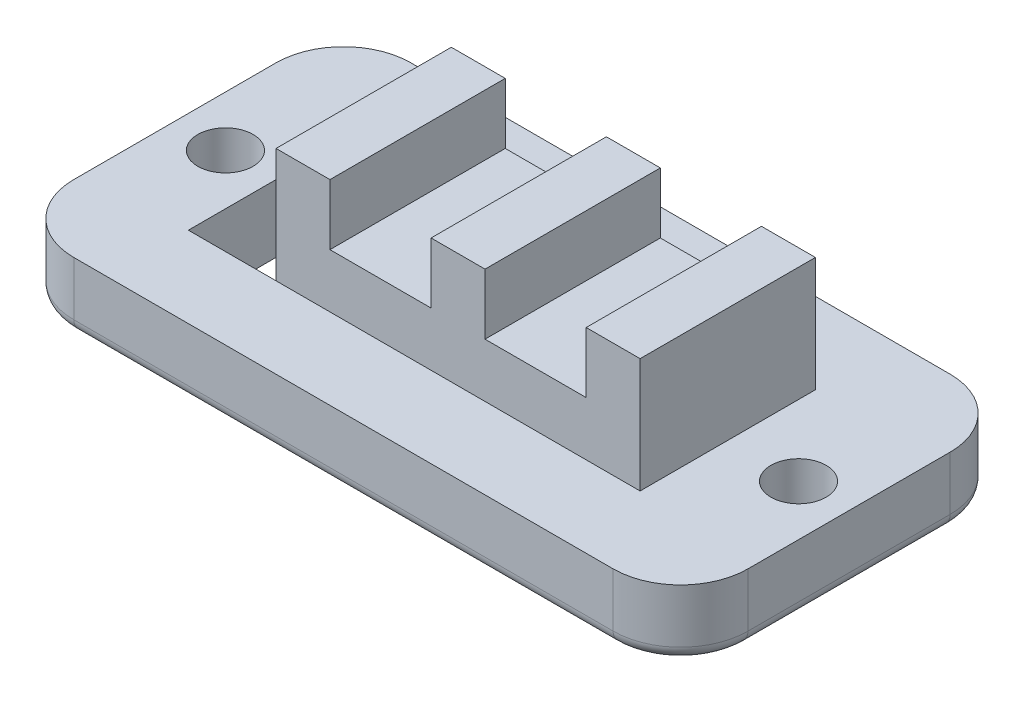
SolidWorks part; units mm, degrees
ref_plane "Front Plane" through (0, 0, 0) normal (0, 0, 1) x (1, 0, 0)
ref_plane "Top Plane" through (0, 0, 0) normal (0, 1, 0) x (1, 0, 0)
ref_plane "Right Plane" through (0, 0, 0) normal (1, 0, 0) x (0, 0, -1)
sketch "Sketch1" plane through (0, 0, 0) normal (0, 1, 0) x (1, 0, 0)
  line L1 (-12.7, -6.35) -> (12.7, -6.35)
  line L2 (-12.7, -6.35) -> (-12.7, 6.35)
  line L3 (-12.7, 6.35) -> (12.7, 6.35)
  line L4 (12.7, -6.35) -> (12.7, 6.35)
  line L5 (-12.7, -6.35) -> (12.7, 6.35) construction
  line L6 (-12.7, 6.35) -> (12.7, -6.35) construction
  point P0 (0, 0)
  dimension "D1" = 25.4
  dimension "D2" = 12.7
extrude "Boss-Extrude1" add sketch "Sketch1" along normal blind 2.54
sketch "Sketch2" plane through (0, 2.54, 0) normal (0, 1, 0) x (1, 0, 0)
  line L0 (12.7, 6.35) -> (-12.7, 6.35) construction
  line L1 (-8.89, -3.302) -> (8.128, -3.302)
  line L2 (-8.89, -3.302) -> (-8.89, 3.302)
  line L3 (-8.89, 3.302) -> (8.128, 3.302)
  line L4 (8.128, -3.302) -> (8.128, 3.302)
  line L5 (-12.7, 6.35) -> (-12.7, -6.35) construction
  line L6 (12.7, -6.35) -> (12.7, 6.35) construction
  line L7 (-12.7, -6.35) -> (12.7, -6.35) construction
  point P0 (0, 0)
  point P8 (0, 0)
  dimension "D1" = 3.048
  dimension "D2" = 3.81
  dimension "D3" = 4.572
  dimension "D4" = 3.048
extrude "Boss-Extrude2" add sketch "Sketch2" along normal blind 2.032
sketch "Sketch3" plane through (0, 0, 0) normal (0, -1, 0) x (1, 0, 0)
  line L0 (-12.7, -6.35) -> (-12.7, 6.35) construction
  line L1 (12.7, 6.35) -> (12.7, -6.35) construction
  circle A0 centre (-10.795, 0) radius 1.0414
  circle A1 centre (10.795, 0) radius 1.0414
  point P6 (-12.7, 0)
extrude "Cut-Extrude1" cut sketch "Sketch3" against normal through all
sketch "Sketch4" plane through (0, 4.572, 0) normal (0, 1, 0) x (1, 0, 0)
  line L0 (8.128, 3.302) -> (-8.89, 3.302) construction
  line L1 (-8.89, -3.302) -> (-5.588, -3.302)
  line L2 (-8.89, -3.302) -> (-8.89, 3.302)
  line L3 (-8.89, 3.302) -> (-5.588, 3.302)
  line L4 (-5.588, -3.302) -> (-5.588, 3.302)
  dimension "D1" = 3.302
extrude "Cut-Extrude2" cut sketch "Sketch4" against normal up to surface (4.572 mm away) up to face at (-10.795, 0, -1.0414)
sketch "Sketch5" plane through (0, 4.572, 0) normal (0, 1, 0) x (1, 0, 0)
  line L0 (8.128, 3.302) -> (-5.588, 3.302) construction
  line L1 (-5.588, 3.302) -> (-3.556, 3.302)
  line L2 (-5.588, 3.302) -> (-5.588, -3.302)
  line L3 (-5.588, -3.302) -> (-3.556, -3.302)
  line L4 (-3.556, 3.302) -> (-3.556, -3.302)
  line L5 (-5.588, -3.302) -> (8.128, -3.302) construction
  line L6 (-5.588, -3.302) -> (-5.588, 3.302) construction
  line L7 (8.128, 3.302) -> (-5.588, 3.302) construction
  line L8 (0.254, 3.302) -> (2.286, 3.302)
  line L9 (0.254, 3.302) -> (0.254, -3.302)
  line L10 (0.254, -3.302) -> (2.286, -3.302)
  line L11 (2.286, 3.302) -> (2.286, -3.302)
  line L12 (8.128, -3.302) -> (8.128, 3.302) construction
  line L18 (6.096, 3.302) -> (8.128, 3.302)
  line L19 (6.096, 3.302) -> (6.096, -3.302)
  line L20 (6.096, -3.302) -> (8.128, -3.302)
  line L21 (8.128, 3.302) -> (8.128, -3.302)
  dimension "D2" = 2.032
  dimension "D4" = 2.032
  dimension "D1" = 2.032
  dimension "D3" = 3.81
sketch "Sketch6" plane through (0, 4.572, 0) normal (0, 1, 0) x (1, 0, 0)
  line L0 (8.128, 3.302) -> (-5.588, 3.302) construction
  line L1 (-1.27, 3.302) -> (0.762, 3.302)
  line L2 (-1.27, 3.302) -> (-1.27, -3.302)
  line L3 (-1.27, -3.302) -> (0.762, -3.302)
  line L4 (0.762, 3.302) -> (0.762, -3.302)
  line L5 (-5.588, -3.302) -> (8.128, -3.302) construction
  line L6 (-3.556, 3.302) -> (-3.556, -3.302) construction
  line L8 (8.128, 3.302) -> (-5.588, 3.302) construction
  line L9 (3.048, 3.302) -> (8.128, 3.302)
  line L10 (3.048, 3.302) -> (3.048, -3.302)
  line L11 (3.048, -3.302) -> (8.128, -3.302)
  line L12 (8.128, 3.302) -> (8.128, -3.302)
  dimension "D1" = 2.032
  dimension "D2" = 2.286
  dimension "D3" = 2.286
extrude "Boss-Extrude3" add sketch "Sketch5" along normal blind 2.286
fillet "Fillet1" radius 2.54 4 edges at (12.7, 1.27, 6.35) (12.7, 1.27, -6.35) (-12.7, 1.27, 6.35) (-12.7, 1.27, -6.35)
fillet "Fillet2" radius 0.508 8 edges at (-11.9561, 0, 5.6061) (-12.7, 0, 0) (-11.9561, 0, -5.6061) (0, 0, -6.35) (11.9561, 0, -5.6061) (12.7, 0, 0) (11.9561, 0, 5.6061) (0, 0, 6.35)
equation "\"D2@Sketch3\"=\"D1@Sketch3\""
equation "\"D4@Sketch5\"=\"D2@Sketch5\""
equation "\"D1@Sketch5\"=\"D2@Sketch5\""
equation "\"D4@Sketch2\"=\"D1@Sketch2\""
